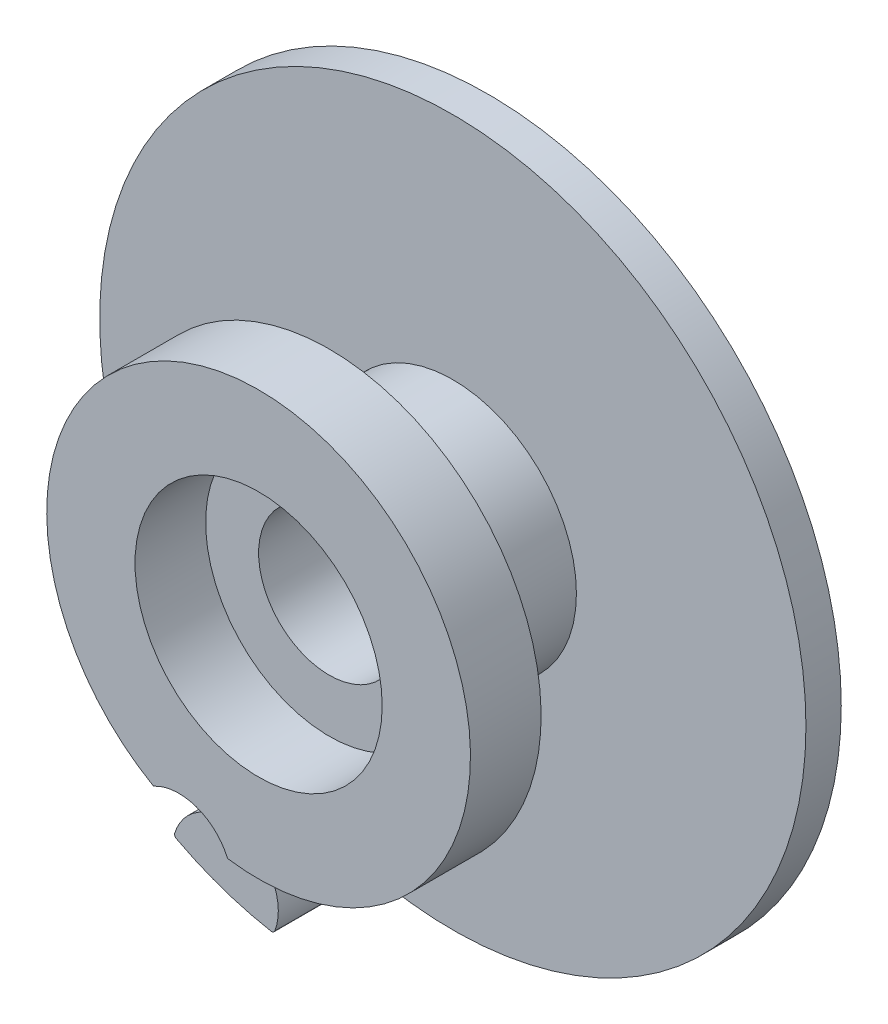
SolidWorks part; units mm, degrees
note: The reader was unsure of these and kept them because the rebuilt part matched: shared geometry of "Sketch1<9>", "Sketch1<10>", "Sketch1<11>".
material "AISI 347 Annealed Stainless Steel (SS)"
ref_plane "Front Plane" through (0, 0, 0) normal (0, 0, 1) x (1, 0, 0)
ref_plane "Top Plane" through (0, 0, 0) normal (0, 1, 0) x (1, 0, 0)
ref_plane "Right Plane" through (0, 0, 0) normal (1, 0, 0) x (0, 0, -1)
sketch "Sketch1" plane through (0, 0, 0) normal (0, 0, 1) x (1, 0, 0)
  line L0 (0, -21.2809) -> (0, 20.8576) construction
  line L1 (-23.4901, 0) -> (24.9244, 0) construction
  line L2 (0, 0) -> (5.5969, 9.6942) construction
  line L3 (0, 0) -> (-5.6466, 9.7801) construction
  line L4 (2.05, 3.5507) -> (-1.6508, 5.6874) construction
  line L5 (-2.05, 3.5507) -> (1.6508, 5.6874) construction
  line L6 (0.8318, 0.175) -> (2.7945, 0.175)
  line L7 (0.8318, -0.175) -> (2.7945, -0.175)
  line L8 (-0.175, 0.8318) -> (-0.175, 2.7945)
  line L9 (0.175, 0.8318) -> (0.175, 2.7945)
  line L10 (0.175, -0.8318) -> (0.175, -2.7945)
  line L11 (-0.175, -0.8318) -> (-0.175, -2.7945)
  line L12 (-0.8318, -0.175) -> (-2.7945, -0.175)
  line L13 (-0.8318, 0.175) -> (-2.7945, 0.175)
  line L14 (0, 0) -> (6.6911, 7.6973) construction
  line L15 (0, 0) -> (-6.6911, 7.6973) construction
  line L16 (0, 4.7343) -> (6.5895, 2.1386) construction
  line L17 (2.6898, 3.0943) -> (2.2024, 3.8667)
  line L18 (0, 0) -> (2.5071, 3.384) construction
  line L19 (2.5071, 3.384) -> (2.4713, 3.3358)
  line L20 (2.6898, 3.0943) -> (1.7172, 2.6408)
  line L21 (3.6667, 2.0717) -> (3.6145, 2.0422)
  line L22 (3.7159, 1.7327) -> (3.5847, 2.6366)
  line L23 (3.7159, 1.7327) -> (2.6429, 1.714)
  line L24 (4.1923, 0.4012) -> (4.1326, 0.3955)
  line L25 (4.0994, 0.0716) -> (4.3472, 0.9506)
  line L26 (4.0994, 0.0716) -> (3.1115, 0.4909)
  line L27 (3.9931, -1.3387) -> (3.9362, -1.3196)
  line L28 (3.7741, -1.602) -> (4.3581, -0.8998)
  line L29 (3.7741, -1.602) -> (3.0422, -0.8171)
  line L30 (3.1034, -2.847) -> (3.0592, -2.8065)
  line L31 (2.7962, -2.9986) -> (3.6153, -2.5945)
  line L32 (2.7962, -2.9986) -> (2.4468, -1.9838)
  line L33 (1.6771, -3.8632) -> (1.6532, -3.8081)
  line L34 (1.3348, -3.8766) -> (2.2475, -3.8407)
  line L35 (1.3348, -3.8766) -> (1.4284, -2.8075)
  line L36 (-0.0392, -4.2113) -> (-0.0387, -4.1513)
  line L37 (-0.3573, -4.0844) -> (0.491, -4.4228)
  line L38 (-0.3573, -4.0844) -> (0.1629, -3.1458)
  line L39 (-1.7487, -3.8313) -> (-1.7238, -3.7767)
  line L40 (-1.9877, -3.5859) -> (-1.3504, -4.2401)
  line L41 (-1.9877, -3.5859) -> (-1.1306, -2.9401)
  line L42 (-3.1558, -2.7888) -> (-3.1109, -2.749)
  line L43 (-3.2744, -2.4674) -> (-2.9582, -3.3243)
  line L44 (-3.2744, -2.4674) -> (-2.2287, -2.226)
  line L45 (-4.0173, -1.2641) -> (-3.9601, -1.2461)
  line L46 (-3.9949, -0.9223) -> (-4.0546, -1.8337)
  line L47 (-3.9949, -0.9223) -> (-2.9415, -1.1271)
  line L48 (-4.1841, 0.4792) -> (-4.1245, 0.4724)
  line L49 (-4.0247, 0.7823) -> (-4.4499, -0.026)
  line L50 (-4.0247, 0.7823) -> (-3.1456, 0.1668)
  line L51 (-3.6275, 2.1396) -> (-3.5758, 2.1091)
  line L52 (-3.3585, 2.3517) -> (-4.0757, 1.7862)
  line L53 (-3.3585, 2.3517) -> (-2.8058, 1.4318)
  line L54 (-2.4436, 3.4301) -> (-2.4088, 3.3812)
  line L55 (-2.1117, 3.5144) -> (-2.9969, 3.2895)
  line L56 (-2.1117, 3.5144) -> (-1.9809, 2.4492)
  line L57 (-0.8372, 4.1274) -> (-0.8253, 4.0686)
  line L58 (-0.4997, 4.0694) -> (-1.3998, 4.2241)
  line L59 (-0.4997, 4.0694) -> (-0.8134, 3.0432)
  line L60 (0.9139, 4.1111) -> (0.9009, 4.0525)
  line L61 (1.1987, 3.9208) -> (0.4393, 4.4282)
  line L62 (1.1987, 3.9208) -> (0.4947, 3.1109)
  line L63 (0, 4.7343) -> (-2.5531, 3.1697) construction
  line L64 (-2.05, 3.5507) -> (-2.4328, 4.7289) construction
  line L65 (-2.0183, 3.4974) -> (-2.5292, 5.0699)
  line L66 (2.5071, 4.3424) -> (3.1715, 5.3462) construction
  line L67 (2.2024, 3.8667) -> (3.1115, 5.2402)
  line L68 (2.5071, 3.384) -> (3.5557, 4.9683)
  line L69 (3.5557, 4.9683) -> (3.1115, 5.2402)
  line L70 (-2.5292, 5.0699) -> (-2.0347, 5.2306)
  line L71 (-2.0347, 5.2306) -> (-1.4785, 3.5187)
  line L72 (-2.1117, 3.5144) -> (-1.2626, 3.7301) construction
  line L73 (-2.0183, 3.4974) -> (-1.4785, 3.5187)
  line L74 (0, 4.7343) -> (-0.7323, 13.1045) construction
  line L75 (3.1336, 5.4612) -> (3.7485, 5.0848)
  line L76 (3.7797, 4.9444) -> (3.2146, 4.0906)
  line L77 (2.998, 5.4311) -> (2.9748, 5.396)
  line L78 (0.067, 6.2631) -> (0.1001, 5.8849)
  line L79 (3.2146, 4.0906) -> (2.93, 3.9142)
  line L80 (2.93, 3.9142) -> (2.88, 3.9474)
  line L81 (-2.6861, 5.2292) -> (-2.0014, 5.4517)
  line L82 (-1.8754, 5.3875) -> (-1.7926, 5.1326)
  line L83 (-2.7504, 5.1032) -> (-2.4797, 4.2702)
  line L84 (-2.4797, 4.2702) -> (-2.2599, 4.0467)
  line L85 (-2.2599, 4.0467) -> (-2.2028, 4.0652)
  line L86 (-0.3315, 6.2283) -> (-0.2984, 5.85)
  line L87 (0.067, 6.2631) -> (-0.3101, 10.5736)
  line L88 (-0.3315, 6.2283) -> (-0.7086, 10.5387)
  line L89 (0, 4.7343) -> (-1.8171, 12.9313) construction
  line L90 (0, 13.1343) -> (-1.0909, 9.5661) construction
  line L91 (-0.2672, 11.2304) -> (-0.2957, 11.5563)
  line L92 (-0.8649, 11.1781) -> (-0.8934, 11.504)
  line L93 (-0.8649, 11.1781) -> (-0.2672, 11.2304)
  line L94 (-0.594, 10.5487) -> (-0.4247, 10.5636)
  line L95 (-0.4247, 10.5636) -> (-0.5426, 11.9112)
  line L96 (-0.5426, 11.9112) -> (-0.6401, 12.0504)
  line L97 (-0.594, 10.5487) -> (-0.7119, 11.8964)
  line L98 (-0.7119, 11.8964) -> (-0.6401, 12.0504)
  line L99 (-0.3655, 10.9201) -> (-0.3219, 10.422)
  line L100 (-0.3219, 10.422) -> (-0.6706, 10.3915)
  line L101 (-0.6706, 10.3915) -> (-0.7142, 10.8896)
  line L102 (-0.7142, 10.8896) -> (-0.3655, 10.9201)
  line L103 (0, 13.1343) -> (-0.5884, 11.4332) construction
  circle A0 centre (0, 0) radius 4.1
  circle A1 centre (0, 4.7343) radius 0.25
  circle A2 centre (0, 0) radius 0.35
  arc A3 (-0.175, 0.8318) -> (-0.8318, 0.175) centre (0, 0) ccw
  arc A4 (-0.175, 2.7945) -> (-2.7945, 0.175) centre (0, 0) ccw
  arc A5 (0.6577, 3.0806) -> (0.4947, 3.1109) centre (0, 0) ccw
  arc A6 (-0.8318, -0.175) -> (-0.175, -0.8318) centre (0, 0) ccw
  arc A7 (0.8318, 0.175) -> (0.175, 0.8318) centre (0, 0) ccw
  arc A8 (0.175, -0.8318) -> (0.8318, -0.175) centre (0, 0) ccw
  arc A9 (-2.7945, -0.175) -> (-0.175, -2.7945) centre (0, 0) ccw
  arc A10 (2.7945, 0.175) -> (0.175, 2.7945) centre (0, 0) ccw
  arc A11 (0.175, -2.7945) -> (2.7945, -0.175) centre (0, 0) ccw
  arc A12 (2.05, 3.5507) -> (1.8799, 6.1728) centre (0, 4.7343) ccw
  circle A13 centre (0, 0) radius 4.2115
  arc A14 (2.4713, 3.3358) -> (2.4182, 3.0865) centre (2.388, 3.2233) cw
  arc A15 (0.6577, 3.0806) -> (2.4182, 3.0865) centre (1.5242, 7.1391) ccw
  arc A16 (1.8538, 2.5467) -> (3.4645, 1.8361) centre (4.2961, 5.902) ccw
  arc A17 (2.7628, 3.1783) -> (2.7631, 3.1784) centre (1.5242, 7.1391) ccw
  arc A18 (3.6145, 2.0422) -> (3.4645, 1.8361) centre (3.4926, 1.9733) cw
  arc A19 (2.7294, 1.5725) -> (3.9118, 0.2683) centre (6.3253, 3.6443) ccw
  arc A20 (4.1326, 0.3955) -> (3.9118, 0.2683) centre (3.9932, 0.3821) cw
  arc A21 (3.133, 0.3264) -> (3.6827, -1.346) centre (7.2607, 0.7565) ccw
  arc A22 (3.9362, -1.3196) -> (3.6827, -1.346) centre (3.8034, -1.2751) cw
  arc A23 (2.995, -0.9761) -> (2.8169, -2.7275) centre (6.9407, -2.2621) ccw
  arc A24 (3.0592, -2.8065) -> (2.8169, -2.7275) centre (2.956, -2.7118) cw
  arc A25 (2.339, -2.1099) -> (1.4639, -3.6375) centre (5.4206, -4.8895) ccw
  arc A26 (1.6532, -3.8081) -> (1.4639, -3.6375) centre (1.5974, -3.6797) cw
  arc A27 (1.2786, -2.8788) -> (-0.1421, -3.9184) centre (2.9632, -6.6715) ccw
  arc A28 (-0.0387, -4.1513) -> (-0.1421, -3.9184) centre (-0.0374, -4.0113) cw
  arc A29 (-0.0028, -3.15) -> (-1.7236, -3.5219) centre (-0.0066, -7.3) ccw
  arc A30 (-1.7238, -3.7767) -> (-1.7236, -3.5219) centre (-1.6657, -3.6493) cw
  arc A31 (-1.2838, -2.8765) -> (-3.007, -2.5163) centre (-2.9752, -6.6662) ccw
  arc A32 (-3.1109, -2.749) -> (-3.007, -2.5163) centre (-3.006, -2.6563) cw
  arc A33 (-2.3428, -2.1057) -> (-3.7706, -1.0757) centre (-5.4293, -4.8798) ccw
  arc A34 (-3.9601, -1.2461) -> (-3.7706, -1.0757) centre (-3.8265, -1.204) cw
  arc A35 (-2.9967, -0.9707) -> (-3.8821, 0.5509) centre (-6.9447, -2.2496) ccw
  arc A36 (-4.1245, 0.4724) -> (-3.8821, 0.5509) centre (-3.9854, 0.4564) cw
  arc A37 (-3.1324, 0.3321) -> (-3.3224, 2.0823) centre (-7.2593, 0.7696) ccw
  arc A38 (-3.5758, 2.1091) -> (-3.3224, 2.0823) centre (-3.4552, 2.038) cw
  arc A39 (-2.7266, 1.5775) -> (-2.1882, 3.2536) centre (-6.3187, 3.6557) ccw
  arc A40 (-2.4088, 3.3812) -> (-2.1882, 3.2536) centre (-2.3276, 3.2672) cw
  arc A41 (-1.8492, 2.5501) -> (-0.6757, 3.8623) centre (-4.2855, 5.9097) ccw
  arc A42 (-0.8253, 4.0686) -> (-0.6757, 3.8623) centre (-0.7975, 3.9314) cw
  arc A43 (-0.6522, 3.0818) -> (0.9537, 3.8033) centre (-1.5113, 7.1418) ccw
  arc A44 (0.9009, 4.0525) -> (0.9537, 3.8033) centre (0.8705, 3.9159) cw
  arc A45 (2.0666, 2.3773) -> (1.575, 2.728) centre (0, 0) ccw
  arc A46 (2.7294, 1.5725) -> (2.6429, 1.714) centre (0, 0) ccw
  arc A47 (3.133, 0.3264) -> (3.1115, 0.4909) centre (0, 0) ccw
  arc A48 (2.995, -0.9761) -> (3.0422, -0.8171) centre (0, 0) ccw
  arc A49 (2.339, -2.1099) -> (2.4468, -1.9838) centre (0, 0) ccw
  arc A50 (-0.6522, 3.0818) -> (-0.8134, 3.0432) centre (0, 0) ccw
  arc A51 (-1.575, 2.728) -> (-2.0666, 2.3773) centre (0, 0) ccw
  arc A52 (-2.7266, 1.5775) -> (-2.8058, 1.4318) centre (0, 0) ccw
  arc A53 (-3.1324, 0.3321) -> (-3.1456, 0.1668) centre (0, 0) ccw
  arc A54 (-2.9967, -0.9707) -> (-2.9415, -1.1271) centre (0, 0) ccw
  arc A55 (-2.3428, -2.1057) -> (-2.2287, -2.226) centre (0, 0) ccw
  arc A56 (-1.2838, -2.8765) -> (-1.1306, -2.9401) centre (0, 0) ccw
  arc A57 (-0.0028, -3.15) -> (0.1629, -3.1458) centre (0, 0) ccw
  arc A58 (1.2786, -2.8788) -> (1.4284, -2.8075) centre (0, 0) ccw
  arc A59 (-2.05, 3.5507) -> (-0.5036, 2.4213) centre (0, 4.7343) ccw
  arc A60 (1.0177, 5.1638) -> (2.0583, 5.0774) centre (1.3569, 2.9395) cw
  arc A61 (0.2412, 4.4152) -> (2.5336, 4.367) centre (1.3569, 2.9395) cw
  arc A62 (-0.2238, 4.4028) -> (-1.7102, 4.232) centre (-0.8673, 3.4497) ccw
  arc A63 (3.7485, 5.0848) -> (3.7797, 4.9444) centre (3.6963, 4.9996) cw
  arc A64 (2.998, 5.4311) -> (3.1336, 5.4612) centre (3.0814, 5.3759) cw
  arc A65 (-0.2238, 4.4028) -> (0.2412, 4.4152) centre (0, 4.7343) ccw
  arc A66 (2.9748, 5.396) -> (2.0583, 5.0774) centre (2.3077, 5.8375) cw
  arc A67 (1.0177, 5.1638) -> (0.1001, 5.8849) centre (0.8971, 5.9546) cw
  arc A68 (-1.8754, 5.3875) -> (-2.0014, 5.4517) centre (-1.9705, 5.3566) ccw
  arc A69 (-2.7504, 5.1032) -> (-2.6861, 5.2292) centre (-2.6552, 5.1341) cw
  arc A70 (-0.2984, 5.85) -> (-0.754, 5.1723) centre (-0.9459, 5.7934) cw
  arc A71 (-1.7926, 5.1326) -> (-1.5095, 5.0037) centre (-1.5211, 5.3535) ccw
  arc A72 (-0.3101, 10.5736) -> (-0.0079, 11.1276) centre (0.2577, 10.6233) cw
  arc A73 (-0.0652, 5.4791) -> (0, 5.5041) centre (-2.8729, 12.8867) ccw
  arc A74 (-1.5095, 5.0037) -> (-0.754, 5.1723) centre (-2.8729, 12.8867) ccw
  arc A75 (-0.0079, 11.1276) -> (0.0594, 11.5321) centre (0.4209, 11.2641) cw
  arc A76 (0.0594, 11.5321) -> (0.2329, 11.9395) centre (-0.7039, 12.0977) ccw
  arc A77 (-0.308, 11.3266) -> (-0.8747, 11.5226) centre (-0.5884, 11.4332) ccw
  circle A78 centre (0, 13.1343) radius 1.2
  circle A79 centre (0, 13.1343) radius 2
  arc A80 (-0.7086, 10.5387) -> (-1.1024, 11.0318) centre (-1.2764, 10.489) ccw
  arc A81 (-1.1024, 11.0318) -> (-1.2389, 11.4185) centre (-1.5484, 11.0918) ccw
  arc A82 (-1.2389, 11.4185) -> (-1.4805, 11.7896) centre (-0.5855, 12.1081) cw
  arc A83 (-1.4805, 11.7896) -> (-0.8934, 11.504) centre (-0.6802, 12.6886) ccw
  arc A84 (0.2329, 11.9395) -> (-0.2957, 11.5563) centre (-0.7114, 12.6858) cw
  circle A85 centre (0, 13.1343) radius 1.8
  arc A86 (-0.865, 11.499) -> (-0.3302, 11.314) centre (0, 13.1343) ccw
  arc A87 (-0.3302, 11.314) -> (-0.308, 11.3266) centre (-0.3267, 11.3337) ccw
  circle A88 centre (0, 13.1343) radius 1.85 construction
  arc A89 (-0.8817, 11.3703) -> (-0.8716, 11.3342) centre (-0.5884, 11.4332) ccw
  arc A90 (-0.865, 11.499) -> (-0.8747, 11.5226) centre (-0.8557, 11.5166) cw
  circle A91 centre (0, 13.1343) radius 0.4
  circle A92 centre (0, 13.1343) radius 0.7
  circle A93 centre (-0.4515, 11.829) radius 0.3
  point P36 (0, 0)
  point P40 (2.5071, 3.384)
  point P180 (0, 0)
  point P182 (-2.0183, 3.4974)
  point P245 (0, 13.1343)
  point P252 (-0.5661, 11.2043)
  point P268 (-0.5661, 11.2043)
  point P273 (-0.5093, 10.5562)
  point P276 (1.85, 13.1343)
  dimension "D1" = 8.2
  dimension "D4" = 0.5
  dimension "D5" = 0.7
  dimension "D6" = 1.7
  dimension "D7" = 5.6
  dimension "D8" = 6.3
  dimension "D17" = 0.14
  dimension "D18" = 8.3
  dimension "D28" = 0.4
  dimension "D29" = 1.85
  dimension "D31" = 1.15
  dimension "D34" = 2.25
  dimension "D37" = 0.1
  dimension "D39" = 0.1
  dimension "D40" = 0.8
  dimension "D41" = 0.8
  dimension "D46" = 0.1
  dimension "D48" = 0.1
  dimension "D52" = 0.35
  dimension "D53" = 0.65
  dimension "D54" = 0.2
  dimension "D55" = 0.95
  dimension "D56" = 0.45
  dimension "D57" = 0.57
  dimension "D58" = 0.2375
  dimension "D61" = 0.6
  dimension "D62" = 2.4
  dimension "D64" = 4
  dimension "D65" = 3.6
  dimension "D70" = 0.05
  dimension "D71" = 0.02
  dimension "D76" = 0.8
  dimension "D77" = 1.4
  dimension "D78" = 0.6
  dimension "D2" = 60
  dimension "D3" = 30
  dimension "D9" = 0.35
  dimension "D11" = 11
  dimension "D12" = 8.5
  dimension "D13" = 0.9133
  dimension "D14" = 0.3425
  dimension "D15" = 0.06
  dimension "D16" = 24
  dimension "D20" = 1.5
  dimension "D21" = 12
  dimension "D22" = 1.8
  dimension "D23" = 3.5
  dimension "D24" = 1.6471
  dimension "D25" = 1.9
  dimension "D26" = 0.52
  dimension "D27" = 12
  dimension "D30" = 0.6
  dimension "D32" = 0.75
  dimension "D33" = 5
  dimension "D35" = 0.2
  dimension "D36" = 0.2
  dimension "D38" = 0.2
  dimension "D42" = 0.06
  dimension "D43" = 1
  dimension "D44" = 0.2
  dimension "D45" = 0.2
  dimension "D47" = 0.2
  dimension "D49" = 0.9
  dimension "D50" = 0.6
  dimension "D51" = 0.06
  dimension "D59" = 1.93
  dimension "D60" = 8.4
  dimension "D63" = 17
  dimension "D66" = 0.17
  dimension "D67" = 1.5
  dimension "D68" = 30
  dimension "D69" = 0.6
  dimension "D72" = 0.35
  dimension "D73" = 0.175
  dimension "D74" = 0.5
  dimension "D75" = 0.15
  dimension "D10" = 4
  dimension "D19" = 15
extrude "Boss-Extrude1" add sketch "Sketch1" along normal blind 0.2 contours A86 A90 A77 A85 A75 A79 A83 L92 A89 L97 | A77 A85 L91 A84 A76 A75 L97 L98 L96 L95 A78 | A78 A91 | L97 A85 L95 A77 | A77 A85 L97 | A77 L95 L96 L98 L97 | L95 A85 A77 | L91 A85 A75 A76 A84 | A85 L91 L93 L95 A79 A75 | A83 A79 L92 | A90 A86 L97 A85 A77 | L97 A86 L95 A85 | A86 A87 A77 A85 L95 | A87 A86 L95 L93 L91 A85 A77 | A86 L97 A79 L93 L95 | L93 A79 L95 | A92 A91 | A78 A93 A77 L97 L98 L96 L95 | L97 A93 L95 A77 | L95 A93 A77 | A78 A93 | A77 A93 L97 | A89 L92 A79
extrude "Boss-Extrude2" add sketch "Sketch1<9>" along normal blind 0.9 contours A92 A91
sketch "Sketch1<9>" plane through (0, 0, 0) normal (0, 0, 1) x (1, 0, 0) same geometry as "Sketch1"
extrude "Boss-Extrude3" add sketch "Sketch1<10>" along normal blind 0.4 from offset 0.9 separate body contours A93 A78 A92
sketch "Sketch1<10>" plane through (0, 0, 0) normal (0, 0, 1) x (1, 0, 0) same geometry as "Sketch1"
extrude "Boss-Extrude4" add sketch "Sketch1<11>" along normal blind 0.9 contours A93 A77 A85 L97 | L97 A93 L95 A77 | A93 L97 A85 L95 | A93 L95 A85 A77 | L95 A93 A77 | A90 A86 L97 A85 A77 | L97 A86 L95 A85 | A86 A87 A77 A85 L95 | A77 A93 L97
sketch "Sketch1<11>" plane through (0, 0, 0) normal (0, 0, 1) x (1, 0, 0) same geometry as "Sketch1"
equation "\"D14@Sketch1\"=\"D13@Sketch1\"*3/8"
